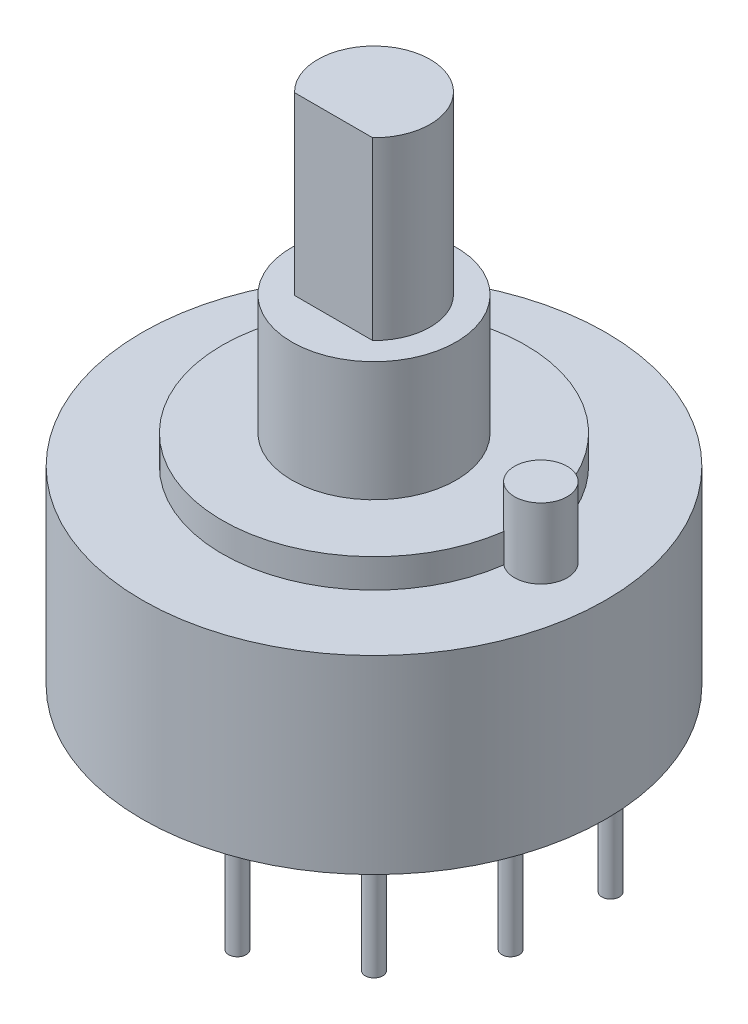
SolidWorks part; units mm, degrees
ref_plane "Front Plane" through (0, 0, 0) normal (0, 0, 1) x (1, 0, 0)
ref_plane "Top Plane" through (0, 0, 0) normal (0, 1, 0) x (1, 0, 0)
ref_plane "Right Plane" through (0, 0, 0) normal (1, 0, 0) x (0, 0, -1)
sketch "Sketch1" plane through (0, 0, 0) normal (1, 0, 0) x (0, 0, -1)
  line L0 (0, 0) -> (-13.2, 0)
  line L1 (-13.2, 0) -> (-13.2, 10.8)
  line L2 (-13.2, 10.8) -> (-8.64, 10.8)
  line L3 (-8.64, 10.8) -> (-8.64, 12.45)
  line L4 (-8.64, 12.45) -> (-4.675, 12.45)
  line L5 (-4.675, 12.45) -> (-4.675, 19.26)
  line L6 (-4.675, 19.26) -> (-3.2, 19.26)
  line L7 (-3.2, 19.26) -> (-3.2, 29.26)
  line L8 (-3.2, 29.26) -> (0, 29.26)
  line L9 (0, 29.26) -> (0, 0)
  line L10 (0, 0) -> (0, -5.9371) construction
  dimension "D1" = 26.4
  dimension "D2" = 10.8
  dimension "D3" = 1.65
  dimension "D4" = 17.28
  dimension "D5" = 9.35
  dimension "D6" = 6.81
  dimension "D7" = 10
  dimension "D8" = 6.4
revolve "Revolve1" add sketch "Sketch1" angle 360 about L10
sketch "Sketch3" plane through (0, 29.26, 0) normal (0, 1, 0) x (1, 0, 0)
  line L1 (-2.2249, -2.3) -> (2.2249, -2.3)
  line L2 (0, -2.3) -> (0, 3.2) construction
  circle A4 centre (0, 0) radius 3.2 construction
  arc A5 (-2.2249, -2.3) -> (2.2249, -2.3) centre (0, 0) ccw
  circle A12 centre (0, 0) radius 3.2 construction
  dimension "D1" = 5.5
extrude "Cut-Extrude1" cut sketch "Sketch3" against normal up to surface (10 mm away) up to face at (0, 19.26, 4.675)
sketch "Sketch6" plane through (0, 10.8, 0) normal (0, 1, 0) x (1, 0, 0)
  circle A4 centre (9.5, 0) radius 1.5
  dimension "D1" = 3
  dimension "D2" = 9.5
extrude "Boss-Extrude3" add sketch "Sketch6" along normal blind 4
sketch "Sketch7" plane through (0, 0, 0) normal (0, -1, 0) x (1, 0, 0)
  line L0 (0, 13.2) -> (0, -13.2) construction
  line L1 (-13.2, 0) -> (13.2, 0) construction
  line L2 (0, 0) -> (-3.4164, -12.7502) construction
  line L3 (0, 0) -> (-9.3338, -9.3338) construction
  line L4 (0, 0) -> (-12.7502, -3.4164) construction
  line L5 (0, 0) -> (-12.7502, 3.4164) construction
  line L6 (0, 0) -> (9.3338, 9.3338) construction
  line L7 (0, 0) -> (12.7502, 3.4164) construction
  line L8 (12.7502, 3.4164) -> (0, 0) construction
  line L9 (0, 0) -> (3.4164, 12.7502) construction
  line L10 (0, 0) -> (12.7502, -3.4164) construction
  circle A0 centre (0, 0) radius 13.2 construction
  circle A1 centre (0, 0) radius 11 construction
  circle A2 centre (-2.847, -10.6252) radius 0.5 construction
  circle A3 centre (-7.7782, -7.7782) radius 0.5 construction
  circle A4 centre (-2.8284, -2.8284) radius 0.5 construction
  circle A5 centre (-10.6252, -2.847) radius 0.5 construction
  circle A6 centre (-10.6252, 2.847) radius 0.5 construction
  circle A7 centre (0, 0) radius 4 construction
  circle A8 centre (2.8284, 2.8284) radius 0.5
  circle A9 centre (2.847, 10.6252) radius 0.5
  circle A10 centre (7.7782, 7.7782) radius 0.5
  circle A11 centre (10.6252, 2.847) radius 0.5
  circle A12 centre (10.6252, -2.847) radius 0.5
  dimension "D5" = 8
  dimension "D6" = 22
  dimension "D7" = 1
  dimension "D1" = 15
  dimension "D2" = 45
  dimension "D3" = 15
  dimension "D4" = 15
extrude "Boss-Extrude4" add sketch "Sketch7" along normal blind 6.3
